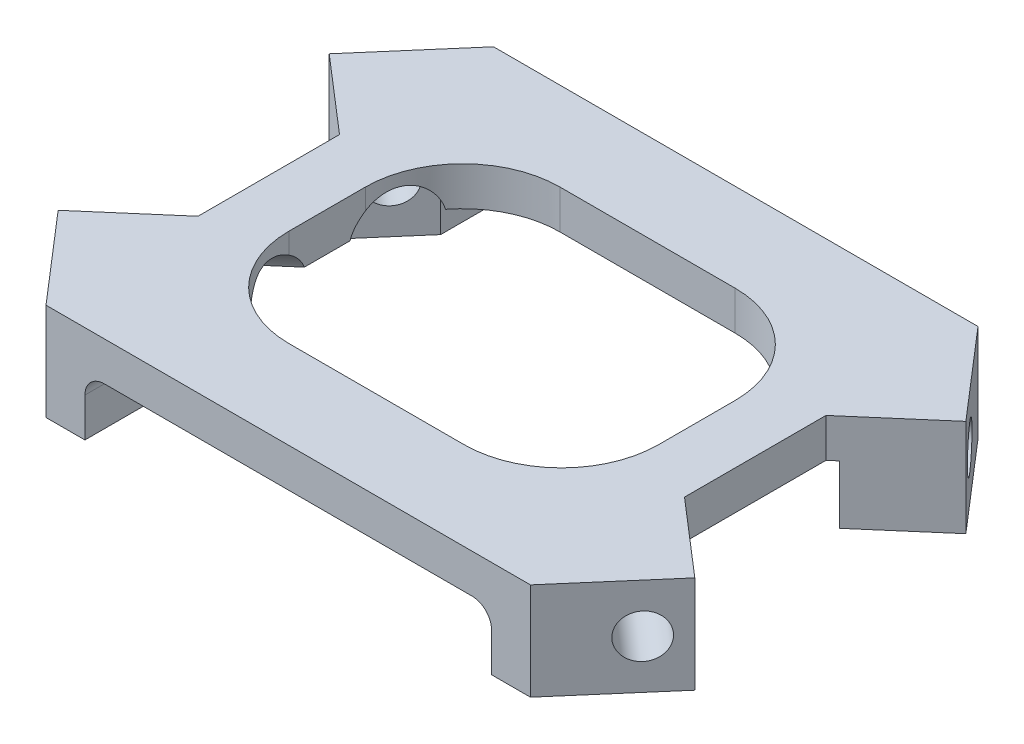
SolidWorks part; units mm, degrees
ref_plane "Front Plane" through (0, 0, 0) normal (0, 0, 1) x (1, 0, 0)
ref_plane "Top Plane" through (0, 0, 0) normal (0, 1, 0) x (1, 0, 0)
ref_plane "Right Plane" through (0, 0, 0) normal (1, 0, 0) x (0, 0, -1)
sketch "Sketch1" plane through (0, 0, 0) normal (0, 1, 0) x (1, 0, 0)
  line L0 (0, 95) -> (-30, 95) construction
  line L1 (0, 130) -> (-150, 130) construction
  line L2 (0, 130) -> (0, -130) construction
  line L3 (0, -130) -> (-150, -130) construction
  line L5 (-30, -80) -> (-30, -85) construction
  line L7 (-30, -10) -> (-169.5228, -130.3307) construction
  line L9 (-169.5228, 130.3307) -> (-153.1953, 149.2624) construction
  line L10 (-153.1953, 149.2624) -> (-30, 80) construction
  line L11 (-150, 130) -> (-161.359, 139.7965) construction
  line L12 (-169.5228, 130.3307) -> (-30, 10) construction
  line L13 (-169.5228, -130.3307) -> (-153.1953, -149.2624) construction
  line L14 (-153.1953, -149.2624) -> (-30, -80) construction
  line L15 (-150, -130) -> (-161.359, -139.7965) construction
  line L16 (-30, 95) -> (-30, 0) construction
  line L17 (-30, 0) -> (-30, -80) construction
  line L18 (-162.9918, 137.9034) -> (-30, 23.2053) construction
  line L19 (-159.8584, 141.5365) -> (-30, 68.5279) construction
  line L20 (-30, 80) -> (-34.9007, 71.2832) construction
  line L29 (-30, 23.2053) -> (-36.531, 15.6326) construction
  line L30 (-150, 130) -> (-138.641, 120.2035) construction
  line L31 (-138.641, 120.2035) -> (-146.8047, 110.7376) construction
  line L32 (-138.641, 120.2035) -> (-133.1788, 126.5368) construction
  line L33 (-133.1788, 126.5368) -> (-128.2781, 135.2536) construction
  line L34 (-30, -85) -> (0, -85) construction
  point P4 (0, 0)
  dimension "D2" = 150
  dimension "D3" = 95
  dimension "D4" = 70
  dimension "D5" = 30
  dimension "D6" = 10
  dimension "D7" = 25
  dimension "D8" = 5
  dimension "D9" = 15
  dimension "D10" = 70
  dimension "D11" = 145.6202
  dimension "D12" = 15
  dimension "D13" = 10
  dimension "D14" = 30
  dimension "D15" = 30
  dimension "D16" = 10
  dimension "D17" = 10
  dimension "D28" = 112.7455
  dimension "D29" = 120
sketch "Sketch2" plane through (0, 0, 0) normal (0, 1, 0) x (1, 0, 0)
  line L0 (-32.7182, 13.929) -> (-24.895, 23)
  line L1 (-24.895, 23) -> (0, 23)
  line L2 (0, 130) -> (0, -130) construction
  line L3 (0, 23) -> (0, 13.929)
  line L4 (0, 13.929) -> (-19, 13.929)
  line L5 (-19, 13.929) -> (-19, 0)
  line L6 (-19, 0) -> (-25, 0)
  line L7 (-25, 0) -> (-25, 7.2724)
  line L8 (-25, 7.2724) -> (-32.7182, 13.929)
  line L9 (-30, 23.2053) -> (-36.531, 15.6326) construction
  line L10 (-30, 95) -> (-30, 0) construction
  point P14 (-27.0722, 9.3237)
  point P15 (-21.2681, 14.0804)
  point P18 (-19.7137, 14.0804)
  dimension "D1" = 4
  dimension "D2" = 1.2
  dimension "D3" = 5
  dimension "D4" = 23
  dimension "D5" = 6
extrude "Boss-Extrude1" add sketch "Sketch2" against normal blind 4
sketch "Sketch3" plane through (0, -4, 0) normal (0, 1, 0) x (-1, 0, 0)
  line L0 (25.7573, -7.9255) -> (32.7182, -13.929)
  line L2 (32.7182, -13.929) -> (24.895, -23)
  line L3 (24.895, -23) -> (20.895, -23)
  line L5 (20.895, -13.5633) -> (25.7573, -7.9255)
  line L6 (20.895, -13.5633) -> (20.895, -23)
  line L8 (0, -23) -> (24.895, -23) construction
  point P2 (-19, -13.0911)
  point P3 (20.1135, -23)
  point P9 (19, -23)
  dimension "D1" = 1
  dimension "D2" = 4
extrude "Boss-Extrude2" add sketch "Sketch3" against normal blind 6
sketch "Sketch4" plane through (-25.6514, 0, -22.1229) normal (-0.7573, 0, -0.6531) x (-0.6531, 0, 0.7573)
  circle A0 centre (7.0204, -5) radius 2.25
  point P2 (0, 0)
  point P3 (7.1578, -1.1641)
  dimension "D2" = 4.5
  dimension "D3" = 5
  dimension "D1" = 5
extrude "Cut-Extrude1" cut sketch "Sketch4" against normal through all
ref_plane "Plane1" through (-17.9332, 0, -15.4664) normal (0.7573, 0, 0.6531) x (0.6531, 0, -0.7573)
sketch "Sketch5" plane through (-18.6904, 0, -16.1195) normal (0.7573, 0, 0.6531) x (0.6531, 0, -0.7573)
  circle A0 centre (-7.0204, -5) radius 3.75
  dimension "D1" = 7.5
extrude "Cut-Extrude2" cut sketch "Sketch5" along normal up to next
fillet "Fillet1" radius 10 1 edges at (-19, -2, -13.929)
fillet "Fillet3" radius 2 1 edges at (-20.895, -4, -18.2817)
mirror "Mirror1" about plane through (0, 0, 0) normal (0, 0, 1) of bodies 126
mirror "Mirror2" about plane through (0, 0, 0) normal (1, 0, 0) of bodies 127
